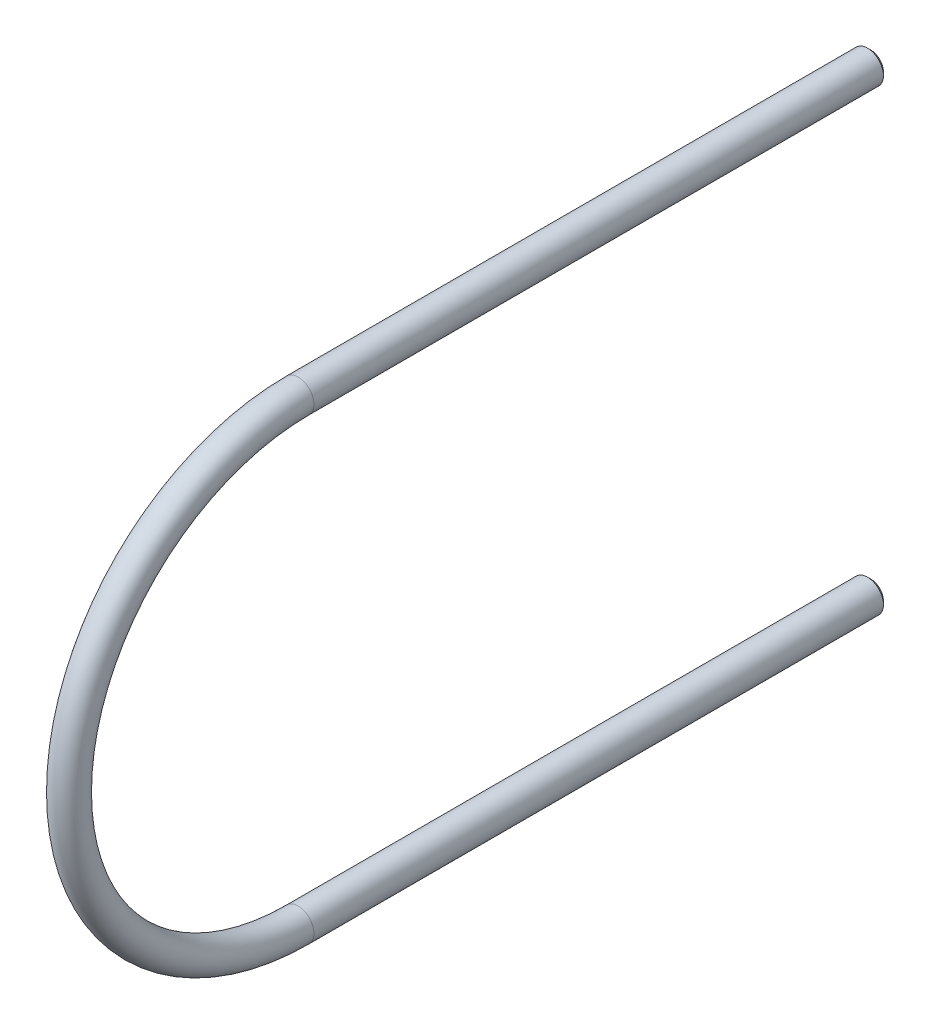
SolidWorks part; units mm, degrees
ref_plane "Front Plane" through (0, 0, 0) normal (0, 0, 1) x (1, 0, 0)
ref_plane "Top Plane" through (0, 0, 0) normal (0, 1, 0) x (1, 0, 0)
ref_plane "Right Plane" through (0, 0, 0) normal (1, 0, 0) x (0, 0, -1)
sketch "Sketch1" plane through (0, 0, 0) normal (0, 0, 1) x (1, 0, 0)
  line L0 (0, 0) -> (0, 36) construction
  line L1 (0, 0) -> (36, 0) construction
  circle A1 centre (0, 36) radius 2.5
revolve "Revolve1" add sketch "Sketch1" angle 180 about L1 other way angle 180
extrude "Boss-Extrude1" add sketch "Sketch1<2>" against normal blind 90
sketch "Sketch1<2>" plane through (0, 0, 0) normal (0, 0, 1) x (1, 0, 0) same geometry as "Sketch1"
sketch "Sketch2" plane through (0, 0, 0) normal (0, 0, -1) x (-1, 0, 0)
  circle A0 centre (0, -36) radius 2.5
extrude "Boss-Extrude2" add sketch "Sketch2" along normal blind 90
chamfer "Chamfer1" distance 0.5 angle 45 2 edges at (0, -33.5, -90) (2.5, 36, -90)
